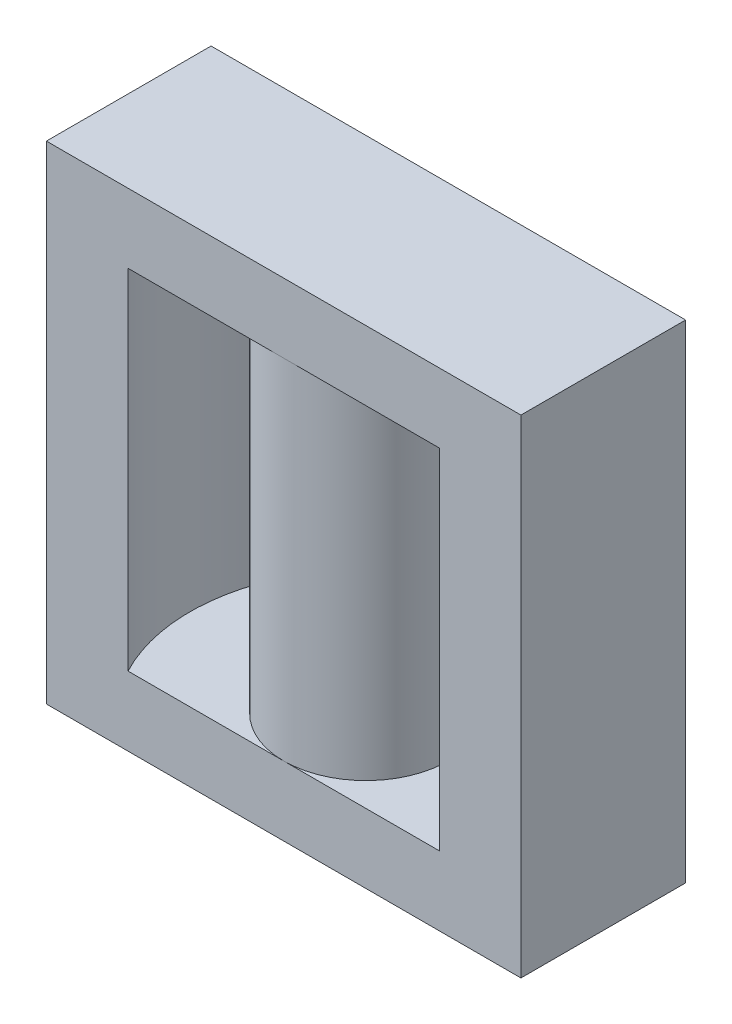
SolidWorks part; units mm, degrees
ref_plane "Front Plane" through (0, 0, 0) normal (0, 0, 1) x (1, 0, 0)
ref_plane "Top Plane" through (0, 0, 0) normal (0, 1, 0) x (1, 0, 0)
ref_plane "Right Plane" through (0, 0, 0) normal (1, 0, 0) x (0, 0, -1)
sketch "Sketch1" plane through (0, 0, 0) normal (0, 1, 0) x (1, 0, 0)
  line L1 (-151.3789, 374.6053) -> (-107.5789, 374.6053)
  line L2 (-151.3789, 374.6053) -> (-151.3789, 359.4053)
  line L3 (-151.3789, 359.4053) -> (-107.5789, 359.4053)
  line L4 (-107.5789, 374.6053) -> (-107.5789, 359.4053)
  circle A0 centre (-129.4789, 367.0053) radius 7.6
  circle A1 centre (-129.4789, 367.0053) radius 16.25
  dimension "D3" = 32.5
  dimension "D4" = 15.2
  dimension "D1" = 43.8
  dimension "D2" = 15.2
  dimension "D5" = 7.6
  dimension "D6" = 21.9
extrude "Boss-Extrude1" add sketch "Sketch1" along normal blind 45 contours A1 L3 L4 L1 | A0 | A1 L1 L2 L3 region at (-148.2224, 0, -367.0053) region at (-129.4789, 0, -367.0053) region at (-110.7355, 0, -367.0053)
extrude "Boss-Extrude2" add sketch "Sketch1<3>" along normal blind 6.4 contours A1 L1 L2 L3 | L1 A1 L3 A0 | A0 | L3 A1 L1 A0 | A1 L3 L4 L1 region at (-148.2224, 0, -367.0053) region at (-140.1489, 0, -367.0053) region at (-118.809, 0, -367.0053) region at (-129.4789, 0, -367.0053) region at (-110.7355, 0, -367.0053)
sketch "Sketch1<3>" plane through (0, 0, 0) normal (0, 1, 0) x (1, 0, 0) same geometry as "Sketch1"
sketch "Sketch2" plane through (0, 45, 0) normal (0, 1, 0) x (1, 0, 0)
  line L1 (-151.3789, 374.6053) -> (-107.5789, 374.6053)
  line L2 (-151.3789, 374.6053) -> (-151.3789, 359.4053)
  line L3 (-151.3789, 359.4053) -> (-107.5789, 359.4053)
  line L4 (-107.5789, 374.6053) -> (-107.5789, 359.4053)
extrude "Boss-Extrude3" add sketch "Sketch2" against normal blind 6.4
